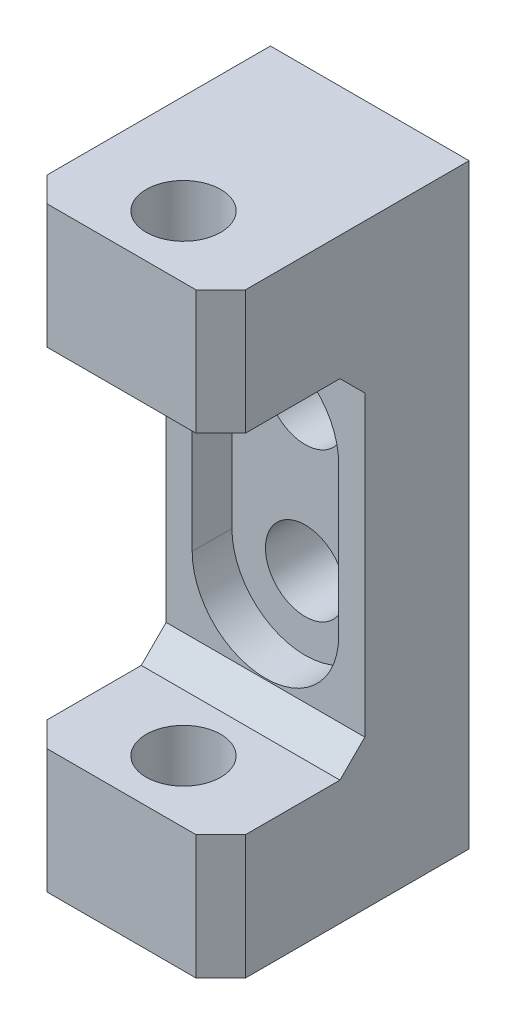
SolidWorks part; units mm, degrees
ref_plane "前视基准面" through (0, 0, 0) normal (0, 0, 1) x (1, 0, 0)
ref_plane "上视基准面" through (0, 0, 0) normal (0, 1, 0) x (1, 0, 0)
ref_plane "右视基准面" through (0, 0, 0) normal (1, 0, 0) x (0, 0, -1)
sketch "草图2" plane through (0, 0, 0) normal (0, 0, 1) x (1, 0, 0)
  line L0 (72, 105) -> (130, 105) construction
  line L1 (104, 105) -> (96, 105)
  line L2 (104, 105) -> (104, 81)
  line L3 (104, 81) -> (96, 81)
  line L4 (96, 105) -> (96, 81)
  line L6 (100, 81) -> (100, 105) construction
  line L7 (130, 105) -> (130, -105) construction
  dimension "D1" = 24
  dimension "D2" = 8
  dimension "D3" = 30
extrude "凸台-拉伸1" add sketch "草图2" along normal blind 10
sketch "草图3" plane through (96, 0, 0) normal (-1, 0, 0) x (0, 0, 1)
  line L0 (0, 93) -> (22.6575, 93) construction
  line L5 (0, 105) -> (0, 81) construction
  line L6 (10, 81) -> (0, 81) construction
  line L7 (4.2, 100) -> (13.3805, 100)
  line L8 (4.2, 100) -> (4.2, 86)
  line L9 (4.2, 86) -> (13.3805, 86)
  line L10 (13.3805, 100) -> (13.3805, 86)
  line L11 (4.2, 100) -> (13.3805, 86) construction
  line L12 (4.2, 86) -> (13.3805, 100) construction
  point P0 (8.7902, 93)
  dimension "D1" = 4.2
  dimension "D2" = 5
extrude "切除-拉伸1" cut sketch "草图3" against normal blind 40
sketch "草图4" plane through (0, 0, 4.2) normal (0, 0, 1) x (1, 0, 0)
  line L0 (100, 100) -> (100, 86) construction
  line L1 (104, 100) -> (96, 100) construction
  line L2 (104, 86) -> (96, 86) construction
  line L3 (100, 93) -> (104, 93) construction
  line L4 (104, 100) -> (104, 86) construction
  circle A0 centre (100, 96) radius 2
  circle A1 centre (100, 90) radius 2
  dimension "D1" = 4
  dimension "D2" = 6
chamfer "倒角1" distance 1 angle 45 2 edges at (100, 86, 4.2) (100, 100, 4.2)
sketch "草图6" plane through (0, 105, 0) normal (0, 1, 0) x (1, 0, 0)
  line L0 (100, -5.2) -> (100, -10) construction
  line L4 (104, -10) -> (104, -5.2)
  line L5 (104, -5.2) -> (96, -5.2)
  line L6 (96, -5.2) -> (96, -10)
  line L7 (96, -10) -> (104, -10)
  line L8 (104, -10) -> (104, -5.2) construction
  line L9 (104, -5.2) -> (96, -5.2) construction
  line L10 (96, -5.2) -> (96, -10) construction
  line L11 (96, -10) -> (104, -10) construction
  circle A1 centre (100, -7.5) radius 1.5
  dimension "D2" = 3
  dimension "D3" = 2.5
  dimension "D1" = 0
hole_wizard "M3 六角头螺栓的柱形沉头孔1" positions "草图7" profile "草图8" counterbore size "M3" standard "GB" end condition through all
sketch "草图7" plane through (124.3639, -131.0101, 4.2) normal (0, 0, 1) x (0, 1, 0)
  point P0 (221.0101, 24.3639)
  point P3 (227.0101, 24.3639)
sketch "草图8" plane through (100, 90, 4.2) normal (1, 0, 0) x (0, -1, 0)
  line L0 (0, 0) -> (0, 4.2)
  line L1 (0, 4.2) -> (1.6, 4.2)
  line L2 (1.6, 4.2) -> (1.6, 1.6)
  line L3 (1.6, 1.6) -> (2.95, 1.6)
  line L4 (2.95, 1.6) -> (2.95, 0)
  line L5 (2.95, 0) -> (0, 0)
  line L6 (0, -6.35) -> (0, 107.95) construction
  dimension "通孔孔直径" = 3.2
  dimension "通孔孔深度" = 4.2
  dimension "柱形沉头孔直径" = 5.9
  dimension "柱形沉头孔深度" = 1.6
sketch "草图11" plane through (0, 0, 4.2) normal (0, 0, 1) x (1, 0, 0)
  line L0 (100, 90) -> (100, 96) construction
  line L1 (97.05, 90) -> (97.05, 96)
  line L2 (102.95, 90) -> (102.95, 96)
  arc A0 (97.05, 90) -> (102.95, 90) centre (100, 90) ccw
  arc A1 (102.95, 96) -> (97.05, 96) centre (100, 96) ccw
  point P2 (100, 93)
  dimension "D1" = 5.9
extrude "切除-拉伸2" cut sketch "草图11" against normal up to surface (1.6 mm away) up to face at (101.6, 90, 2.6)
hole_wizard "大小mm 暗销孔2" positions "草图12" profile "草图13" hole size "Ø3.0" standard "GB"
sketch "草图12" plane through (124.3639, 105, -5) normal (0, 1, 0) x (-1, 0, 0)
  point P0 (24.3639, 12.5)
sketch "草图13" plane through (100, 105, 7.5) normal (1, 0, 0) x (0, 0, 1)
  line L0 (0, 0) -> (0, 24.9013)
  line L1 (0, 24.9013) -> (1.5, 24)
  line L2 (1.5, 24) -> (1.5, 0)
  line L3 (1.5, 0) -> (0, 0)
  line L4 (0, 24.9013) -> (-1.5, 24) construction
  line L5 (0, -6.35) -> (0, 107.95) construction
  dimension "孔直径" = 3
  dimension "孔深度" = 24
  dimension "导头角度" = 118
chamfer "倒角2" distance 1 angle 45 4 edges at (96, 83.5, 10) (104, 83.5, 10) (104, 102.5, 10) (96, 102.5, 10)
